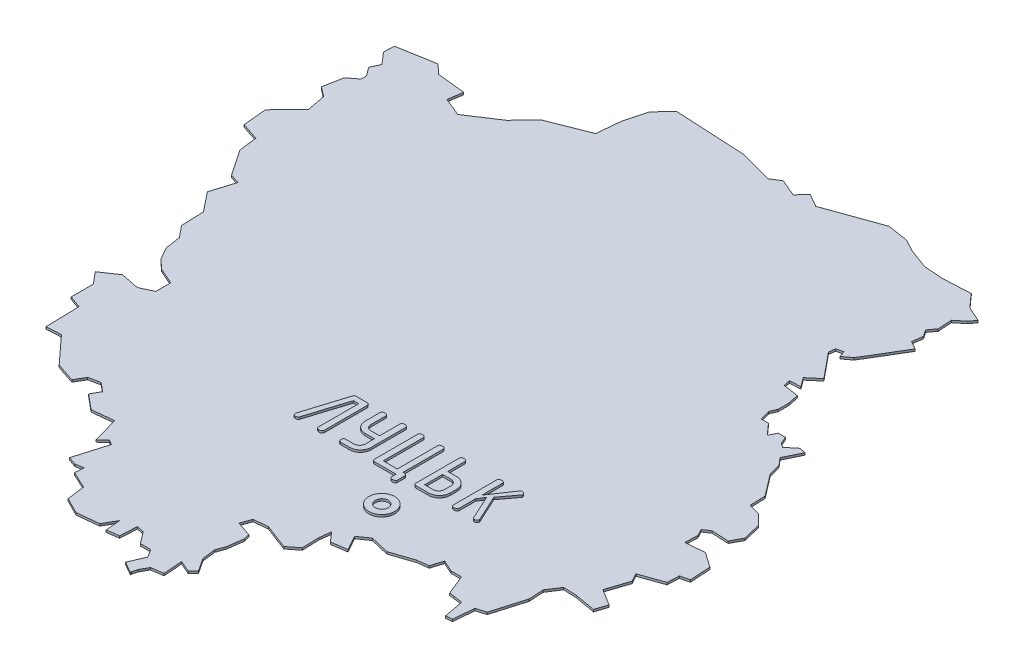
SolidWorks part; units mm, degrees
ref_plane "Спереди" through (0, 0, 0) normal (0, 0, 1) x (1, 0, 0)
ref_plane "Сверху" through (0, 0, 0) normal (0, 1, 0) x (1, 0, 0)
ref_plane "Справа" through (0, 0, 0) normal (1, 0, 0) x (0, 0, -1)
sketch "Эскиз1" plane through (0, 0, 0) normal (0, 1, 0) x (1, 0, 0)
  line B0 (-8480.3259, 8945.7632) -> (-8524.4635, 8941.8693)
  line B1 (-8524.4635, 8941.8693) -> (-8523.1427, 8971.0692)
  line B2 (-8523.1427, 8971.0692) -> (-8531.5781, 8986.6546)
  line B3 (-8531.5781, 8986.6546) -> (-8516.0028, 8997.0229)
  line B4 (-8516.0028, 8997.0229) -> (-8477.0976, 8995.0722)
  line B5 (-8477.0976, 8995.0722) -> (-8463.4527, 9020.3909)
  line B6 (-8463.4527, 9020.3909) -> (-8473.186, 9061.2874)
  line B7 (-8473.186, 9061.2874) -> (-8497.1992, 9085.2904)
  line B8 (-8497.1992, 9085.2904) -> (-8523.1427, 9092.4177)
  line B9 (-8523.1427, 9092.4177) -> (-8524.4635, 9128.125)
  line B10 (-8524.4635, 9128.125) -> (-8562.0733, 9177.4315)
  line B11 (-8562.0733, 9177.4315) -> (-8570.534, 9206.6415)
  line B12 (-8570.534, 9206.6415) -> (-8584.1535, 9222.1964)
  line B13 (-8584.1535, 9222.1964) -> (-8565.3499, 9261.1524)
  line B14 (-8565.3499, 9261.1524) -> (-8579.6044, 9264.4011)
  line B15 (-8579.6044, 9264.4011) -> (-8601.6668, 9246.2223)
  line B16 (-8601.6668, 9246.2223) -> (-8611.4153, 9252.7095)
  line B17 (-8611.4153, 9252.7095) -> (-8618.5527, 9269.5776)
  line B18 (-8618.5527, 9269.5776) -> (-8635.4183, 9269.5776)
  line B19 (-8635.4183, 9269.5776) -> (-8643.8588, 9252.7095)
  line B20 (-8643.8588, 9252.7095) -> (-8666.5765, 9278.0155)
  line B21 (-8666.5765, 9278.0155) -> (-8683.432, 9278.0155)
  line B22 (-8683.432, 9278.0155) -> (-8683.432, 9278.653)
  line B23 (-8683.432, 9278.653) -> (-8689.9293, 9302.0261)
  line B24 (-8689.9293, 9302.0261) -> (-8683.432, 9316.9715)
  line B25 (-8683.432, 9316.9715) -> (-8683.432, 9342.2775)
  line B26 (-8683.432, 9342.2775) -> (-8688.639, 9366.9282)
  line B27 (-8688.639, 9366.9282) -> (-8724.3234, 9372.125)
  line B28 (-8724.3234, 9372.125) -> (-8727.5721, 9387.6825)
  line B29 (-8727.5721, 9387.6825) -> (-8702.261, 9388.983)
  line B30 (-8702.261, 9388.983) -> (-8717.8388, 9409.7627)
  line B31 (-8717.8388, 9409.7627) -> (-8691.8825, 9431.8252)
  line B32 (-8691.8825, 9431.8252) -> (-8739.9139, 9490.2223)
  line B33 (-8739.9139, 9490.2223) -> (-8737.9581, 9505.1397)
  line B34 (-8737.9581, 9505.1397) -> (-8722.3727, 9509.031)
  line B35 (-8722.3727, 9509.031) -> (-8717.8388, 9494.7562)
  line B36 (-8717.8388, 9494.7562) -> (-8699.0047, 9509.031)
  line B37 (-8699.0047, 9509.031) -> (-8683.432, 9534.3624)
  line B38 (-8683.432, 9534.3624) -> (-8645.8095, 9597.3011)
  line B39 (-8645.8095, 9597.3011) -> (-8664.6258, 9607.677)
  line B40 (-8664.6258, 9607.677) -> (-8661.3644, 9631.6851)
  line B41 (-8661.3644, 9631.6851) -> (-8671.7607, 9647.2654)
  line B42 (-8671.7607, 9647.2654) -> (-8659.4213, 9664.126)
  line B43 (-8659.4213, 9664.126) -> (-8661.3644, 9696.5745)
  line B44 (-8661.3644, 9696.5745) -> (-8640.6203, 9713.4553)
  line B45 (-8640.6203, 9713.4553) -> (-8630.2139, 9727.0875)
  line B46 (-8630.2139, 9727.0875) -> (-8664.6258, 9742.6678)
  line B47 (-8664.6258, 9742.6678) -> (-8683.432, 9763.4425)
  line B48 (-8683.432, 9763.4425) -> (-8691.8825, 9773.1605)
  line B49 (-8691.8825, 9773.1605) -> (-8756.7541, 9769.9144)
  line B50 (-8756.7541, 9769.9144) -> (-8799.5912, 9773.1605)
  line B51 (-8799.5912, 9773.1605) -> (-8845.6643, 9790.0185)
  line B52 (-8845.6643, 9790.0185) -> (-8874.2266, 9805.6014)
  line B53 (-8874.2266, 9805.6014) -> (-8922.2402, 9812.7464)
  line B54 (-8922.2402, 9812.7464) -> (-9046.8475, 9767.9612)
  line B55 (-9046.8475, 9767.9612) -> (-9077.3479, 9785.4973)
  line B56 (-9077.3479, 9785.4973) -> (-9096.1667, 9764.7303)
  line B57 (-9096.1667, 9764.7303) -> (-9135.7475, 9781.6086)
  line B58 (-9135.7475, 9781.6086) -> (-9157.81, 9767.9612)
  line B59 (-9157.81, 9767.9612) -> (-9234.3884, 9788.7206)
  line B60 (-9234.3884, 9788.7206) -> (-9299.288, 9791.9692)
  line B61 (-9299.288, 9791.9692) -> (-9398.569, 9797.1661)
  line B62 (-9398.569, 9797.1661) -> (-9429.0769, 9764.7303)
  line B63 (-9429.0769, 9764.7303) -> (-9442.6862, 9713.4553)
  line B64 (-9442.6862, 9713.4553) -> (-9447.8805, 9658.9418)
  line B65 (-9447.8805, 9658.9418) -> (-9538.7287, 9623.2574)
  line B66 (-9538.7287, 9623.2574) -> (-9577.6872, 9582.3761)
  line B67 (-9577.6872, 9582.3761) -> (-9645.8253, 9537.5857)
  line B68 (-9645.8253, 9537.5857) -> (-9688.6497, 9555.1193)
  line B69 (-9688.6497, 9555.1193) -> (-9683.4477, 9588.8556)
  line B70 (-9683.4477, 9588.8556) -> (-9748.3371, 9596.0006)
  line B71 (-9748.3371, 9596.0006) -> (-9770.4072, 9616.12)
  line B72 (-9770.4072, 9616.12) -> (-9856.0738, 9601.1797)
  line B73 (-9856.0738, 9601.1797) -> (-9857.3565, 9577.1741)
  line B74 (-9857.3565, 9577.1741) -> (-9834.0189, 9549.9276)
  line B75 (-9834.0189, 9549.9276) -> (-9843.7344, 9529.158)
  line B76 (-9843.7344, 9529.158) -> (-9828.8069, 9509.031)
  line B77 (-9828.8069, 9509.031) -> (-9828.8069, 9496.7146)
  line B78 (-9828.8069, 9496.7146) -> (-9850.8718, 9479.8413)
  line B79 (-9850.8718, 9479.8413) -> (-9859.3123, 9435.0637)
  line B80 (-9859.3123, 9435.0637) -> (-9837.2422, 9418.1828)
  line B81 (-9837.2422, 9418.1828) -> (-9828.8069, 9375.3661)
  line B82 (-9828.8069, 9375.3661) -> (-9878.1286, 9324.0962)
  line B83 (-9878.1286, 9324.0962) -> (-9872.9394, 9269.5776)
  line B84 (-9872.9394, 9269.5776) -> (-9832.0606, 9255.9708)
  line B85 (-9832.0606, 9255.9708) -> (-9826.8638, 9213.7738)
  line B86 (-9826.8638, 9213.7738) -> (-9785.985, 9153.4158)
  line B87 (-9785.985, 9153.4158) -> (-9763.92, 9146.9362)
  line B88 (-9763.92, 9146.9362) -> (-9780.7805, 9092.4177)
  line B89 (-9780.7805, 9092.4177) -> (-9745.0859, 9047.6502)
  line B90 (-9745.0859, 9047.6502) -> (-9743.1682, 8995.0722)
  line B91 (-9743.1682, 8995.0722) -> (-9721.088, 8967.8231)
  line B92 (-9721.088, 8967.8231) -> (-9715.8912, 8932.1284)
  line B93 (-9715.8912, 8932.1284) -> (-9699.0306, 8902.9337)
  line B94 (-9699.0306, 8902.9337) -> (-9678.2458, 8884.1199)
  line B95 (-9678.2458, 8884.1199) -> (-9640.6081, 8867.2492)
  line B96 (-9640.6081, 8867.2492) -> (-9640.6081, 8832.8373)
  line B97 (-9640.6081, 8832.8373) -> (-9669.8257, 8819.228)
  line B98 (-9669.8257, 8819.228) -> (-9712.6476, 8827.6608)
  line B99 (-9712.6476, 8827.6608) -> (-9750.2878, 8802.3471)
  line B100 (-9750.2878, 8802.3471) -> (-9727.5802, 8775.1056)
  line B101 (-9727.5802, 8775.1056) -> (-9727.5802, 8723.8307)
  line B102 (-9727.5802, 8723.8307) -> (-9699.0306, 8713.4497)
  line B103 (-9699.0306, 8713.4497) -> (-9697.0723, 8634.9205)
  line B104 (-9697.0723, 8634.9205) -> (-9663.3182, 8636.8738)
  line B105 (-9663.3182, 8636.8738) -> (-9604.9236, 8573.2747)
  line B106 (-9604.9236, 8573.2747) -> (-9560.8064, 8558.3497)
  line B107 (-9560.8064, 8558.3497) -> (-9547.1717, 8581.7151)
  line B108 (-9547.1717, 8581.7151) -> (-9521.2281, 8586.9069)
  line B109 (-9521.2281, 8586.9069) -> (-9501.1011, 8570.0337)
  line B110 (-9501.1011, 8570.0337) -> (-9512.7801, 8549.2717)
  line B111 (-9512.7801, 8549.2717) -> (-9478.3935, 8520.7119)
  line B112 (-9478.3935, 8520.7119) -> (-9429.0769, 8525.9037)
  line B113 (-9429.0769, 8525.9037) -> (-9412.191, 8466.1985)
  line B114 (-9412.191, 8466.1985) -> (-9396.6386, 8481.1235)
  line B115 (-9396.6386, 8481.1235) -> (-9384.9342, 8474.6287)
  line B116 (-9384.9342, 8474.6287) -> (-9407.0068, 8399.3584)
  line B117 (-9407.0068, 8399.3584) -> (-9388.188, 8392.8788)
  line B118 (-9388.188, 8392.8788) -> (-9369.3742, 8396.1122)
  line B119 (-9369.3742, 8396.1122) -> (-9371.3097, 8375.3452)
  line B120 (-9371.3097, 8375.3452) -> (-9331.7314, 8356.5314)
  line B121 (-9331.7314, 8356.5314) -> (-9326.5422, 8315.6374)
  line B122 (-9326.5422, 8315.6374) -> (-9289.5522, 8296.8236)
  line B123 (-9289.5522, 8296.8236) -> (-9239.57, 8302.0052)
  line B124 (-9239.57, 8302.0052) -> (-9222.7171, 8331.2279)
  line B125 (-9222.7171, 8331.2279) -> (-9219.4685, 8296.8236)
  line B126 (-9219.4685, 8296.8236) -> (-9192.1889, 8300.7276)
  line B127 (-9192.1889, 8300.7276) -> (-9190.2636, 8339.6607)
  line B128 (-9190.2636, 8339.6607) -> (-9173.398, 8336.4172)
  line B129 (-9173.398, 8336.4172) -> (-9152.6208, 8309.1604)
  line B130 (-9152.6208, 8309.1604) -> (-9128.5949, 8309.1604)
  line B131 (-9128.5949, 8309.1604) -> (-9116.9185, 8290.339)
  line B132 (-9116.9185, 8290.339) -> (-9132.4989, 8254.6419)
  line B133 (-9132.4989, 8254.6419) -> (-9105.2421, 8239.0793)
  line B134 (-9105.2421, 8239.0793) -> (-9106.5452, 8242.3051)
  line B135 (-9106.5452, 8242.3051) -> (-9103.3092, 8254.6419)
  line B136 (-9103.3092, 8254.6419) -> (-9092.9104, 8272.8156)
  line B137 (-9092.9104, 8272.8156) -> (-9065.6613, 8276.7297)
  line B138 (-9065.6613, 8276.7297) -> (-9068.9024, 8320.8444)
  line B139 (-9068.9024, 8320.8444) -> (-9041.6507, 8309.1604)
  line B140 (-9041.6507, 8309.1604) -> (-9029.9845, 8320.8444)
  line B141 (-9029.9845, 8320.8444) -> (-9050.0937, 8351.3295)
  line B142 (-9050.0937, 8351.3295) -> (-9053.9748, 8382.4851)
  line B143 (-9053.9748, 8382.4851) -> (-9046.8475, 8402.6096)
  line B144 (-9046.8475, 8402.6096) -> (-9041.6507, 8438.9443)
  line B145 (-9041.6507, 8438.9443) -> (-9044.8968, 8452.5739)
  line B146 (-9044.8968, 8452.5739) -> (-9079.3113, 8464.2706)
  line B147 (-9079.3113, 8464.2706) -> (-9070.8556, 8488.2584)
  line B148 (-9070.8556, 8488.2584) -> (-9038.3944, 8491.5121)
  line B149 (-9038.3944, 8491.5121) -> (-8980.6501, 8469.4395)
  line B150 (-8980.6501, 8469.4395) -> (-8956.6394, 8488.2584)
  line B151 (-8956.6394, 8488.2584) -> (-8957.9323, 8527.2093)
  line B152 (-8957.9323, 8527.2093) -> (-8954.7014, 8554.4431)
  line B153 (-8954.7014, 8554.4431) -> (-8935.8826, 8532.4036)
  line B154 (-8935.8826, 8532.4036) -> (-8900.1803, 8537.5775)
  line B155 (-8900.1803, 8537.5775) -> (-8919.0068, 8571.9717)
  line B156 (-8919.0068, 8571.9717) -> (-8895.0038, 8588.8424)
  line B157 (-8895.0038, 8588.8424) -> (-8850.8662, 8578.4715)
  line B158 (-8850.8662, 8578.4715) -> (-8799.5912, 8595.9747)
  line B159 (-8799.5912, 8595.9747) -> (-8773.6426, 8599.2437)
  line B160 (-8773.6426, 8599.2437) -> (-8765.2047, 8626.4902)
  line B161 (-8765.2047, 8626.4902) -> (-8737.9581, 8614.1484)
  line B162 (-8737.9581, 8614.1484) -> (-8713.9551, 8614.1484)
  line B163 (-8713.9551, 8614.1484) -> (-8695.116, 8568.0829)
  line B164 (-8695.116, 8568.0829) -> (-8683.432, 8566.7774)
  line B165 (-8683.432, 8566.7774) -> (-8662.6725, 8563.5414)
  line B166 (-8662.6725, 8563.5414) -> (-8654.2423, 8517.4684)
  line B167 (-8654.2423, 8517.4684) -> (-8639.3096, 8518.746)
  line B168 (-8639.3096, 8518.746) -> (-8635.4183, 8566.7774)
  line B169 (-8635.4183, 8566.7774) -> (-8613.3635, 8573.2747)
  line B170 (-8613.3635, 8573.2747) -> (-8591.2858, 8648.5425)
  line B171 (-8591.2858, 8648.5425) -> (-8593.2391, 8682.9417)
  line B172 (-8593.2391, 8682.9417) -> (-8574.4228, 8711.504)
  line B173 (-8574.4228, 8711.504) -> (-8543.2671, 8710.2036)
  line B174 (-8543.2671, 8710.2036) -> (-8495.9012, 8701.7555)
  line B175 (-8495.9012, 8701.7555) -> (-8486.8055, 8729.0173)
  line B176 (-8486.8055, 8729.0173) -> (-8524.4635, 8752.3904)
  line B177 (-8524.4635, 8752.3904) -> (-8507.5649, 8803.6502)
  line B178 (-8507.5649, 8803.6502) -> (-8517.9586, 8822.4639)
  line B179 (-8517.9586, 8822.4639) -> (-8464.7481, 8841.298)
  line B180 (-8464.7481, 8841.298) -> (-8463.4527, 8868.5472)
  line B181 (-8463.4527, 8868.5472) -> (-8442.6679, 8873.7288)
  line B182 (-8442.6679, 8873.7288) -> (-8445.9445, 8921.7475)
  line B183 (-8445.9445, 8921.7475) -> (-8480.3259, 8945.7632)
sketch_block_instance "Блок25-1"
sketch_block "Блок25"
extrude "Бобышка-Вытянуть1" add sketch "Эскиз1" along normal blind 5 contours B182 B183 B0 B1 B2 B3 B4 B5 B6 B7 B8 B9 B10 B11 B12 B13 B14 B15 B16 B17 B18 B19 B20 B21 B22 B23 B24 B25 B26 B27 B28 B29 B30 B31 B32 B33 B34 B35 B36 B37 B38 B39 B40 B41 B42 B43 B44 B45 B46 B47 B48 region at (-9164.3905, 0, -9103.0962)
sketch "Эскиз2" plane through (0, 0, 0) normal (0, 1, 0) x (1, 0, 0)
  line L0 (-9236.356, 8739.4816) -> (-8693.2049, 8739.4816) construction
  circle A0 centre (-8947.3825, 8663.2073) radius 15
  circle A1 centre (-8947.3825, 8663.2073) radius 30
  text T0 "<b>ЛУЦЬК</b>" font "GOST Type AU" height 110
  dimension "D1" = 30
  dimension "D2" = 60
extrude "Бобышка-Вытянуть2" add sketch "Эскиз2" along normal blind 10
scale "Масштаб1" scale about centroid uniform scaling yes scale factor 0.05
